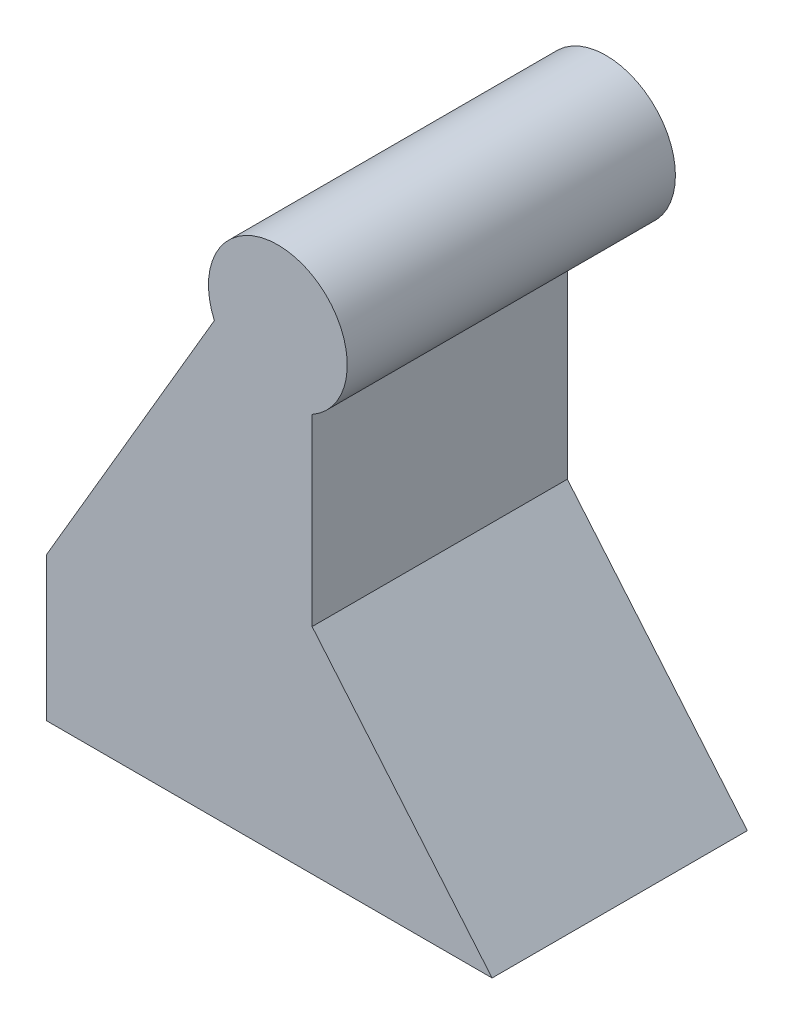
SolidWorks part; units mm, degrees
material "Chrome Stainless Steel"
ref_plane "Front Plane" through (0, 0, 0) normal (0, 0, 1) x (1, 0, 0)
ref_plane "Top Plane" through (0, 0, 0) normal (0, 1, 0) x (1, 0, 0)
ref_plane "Right Plane" through (0, 0, 0) normal (1, 0, 0) x (0, 0, -1)
sketch "Sketch1" plane through (0, 0, 0) normal (0, 0, 1) x (1, 0, 0)
  circle A0 centre (-74.3158, -7.95) radius 9.5167
  circle A2 centre (-74.3158, -7.95) radius 4.3097
extrude "Extrude1" add sketch "Sketch1" along normal blind 10 and the other way blind 10
sketch "Sketch2" plane through (0, 0, 10) normal (0, 0, 1) x (1, 0, 0)
  line L0 (-83.0257, -11.7849) -> (-106.0197, -51.0473)
  line L1 (-106.0197, -51.0473) -> (-106.0197, -70.8154)
  line L3 (-106.0197, -70.8154) -> (-44.9385, -70.8154)
  line L4 (-44.9385, -70.8154) -> (-69.6204, -41.4234)
  line L5 (-69.6204, -41.4234) -> (-69.6204, -16.2278)
  circle A0 centre (-74.3158, -7.95) radius 9.5167 construction
  arc A1 (-83.0257, -11.7849) -> (-69.6204, -16.2278) centre (-74.3158, -7.95) ccw
extrude "Extrude2" add sketch "Sketch2" along normal blind 25 and the other way blind 10
sketch "Sketch3" plane through (0, 0, 10) normal (0, 0, 1) x (1, 0, 0)
  arc A0 (-83.0257, -11.7849) -> (-69.6204, -16.2278) centre (-74.3158, -7.95) ccw construction
  arc A1 (-69.6204, -16.2278) -> (-83.0257, -11.7849) centre (-74.3158, -7.95) ccw construction
  arc A2 (-83.0257, -11.7849) -> (-69.6204, -16.2278) centre (-74.3158, -7.95) ccw
  arc A3 (-69.6204, -16.2278) -> (-83.0257, -11.7849) centre (-74.3158, -7.95) ccw
extrude "Extrude3" add sketch "Sketch3" along normal up to surface (25 mm away) up to face at (-80.0385, -44.1819, 35)
